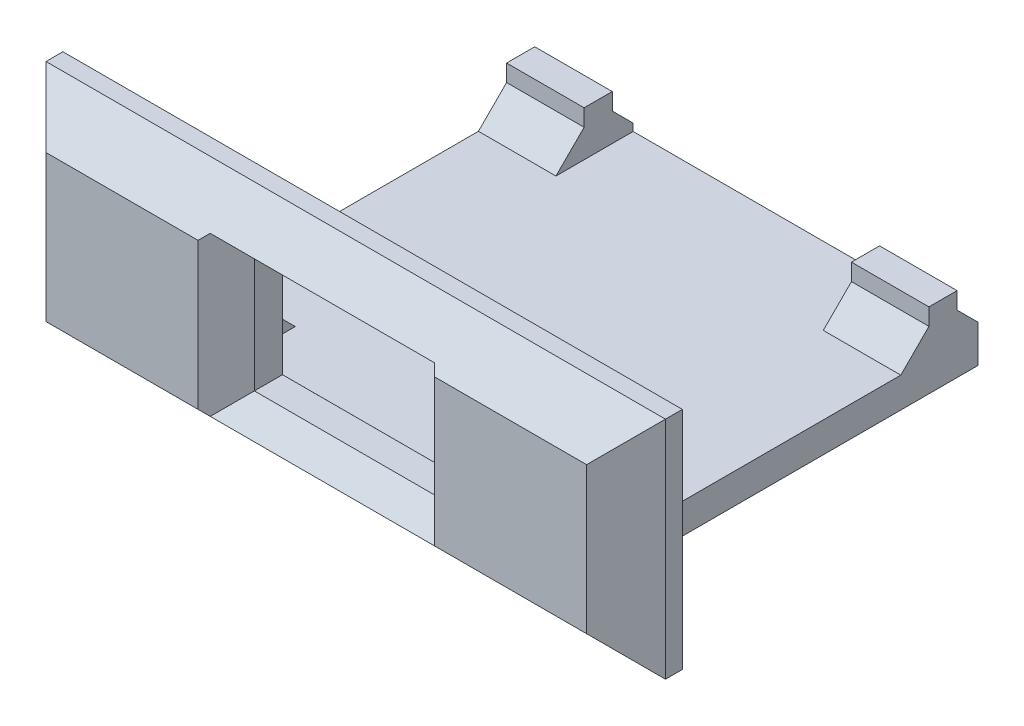
SolidWorks part; units mm, degrees
ref_plane "Спереди" through (0, 0, 0) normal (0, 0, 1) x (1, 0, 0)
ref_plane "Сверху" through (0, 0, 0) normal (0, 1, 0) x (1, 0, 0)
ref_plane "Справа" through (0, 0, 0) normal (1, 0, 0) x (0, 0, -1)
ref_plane "Плоскость4" through (0, 0, 727.8525) normal (0, 0, 1) x (1, 0, 0)
sketch "Эскиз1" plane through (0, 0, 727.8525) normal (0, 0, 1) x (1, 0, 0)
  line L0 (-220.0776, -84.8681) -> (-220.0776, -72.8681)
  line L1 (-208.0776, -72.8681) -> (-122.0776, -72.8681)
  line L2 (-220.0776, -84.8681) -> (-220.0776, -100.8681)
  line L3 (-208.0776, -112.8681) -> (-122.0776, -112.8681)
  line L4 (-110.0776, -84.8681) -> (-110.0776, -100.8681)
  line L5 (-208.0776, -72.8681) -> (-220.0776, -72.8681)
  line L6 (-122.0776, -72.8681) -> (-110.0776, -72.8681)
  line L7 (-110.0776, -84.8681) -> (-110.0776, -72.8681)
  line L8 (-208.0776, -112.8681) -> (-220.0776, -112.8681)
  line L9 (-220.0776, -100.8681) -> (-220.0776, -112.8681)
  line L10 (-110.0776, -100.8681) -> (-110.0776, -112.8681)
  line L11 (-122.0776, -112.8681) -> (-110.0776, -112.8681)
  point P6 (-110.0776, -112.8681)
  point P11 (-220.0776, -112.8681)
  point P14 (-220.0776, -72.8681)
  dimension "D1" = 110
  dimension "D2" = 40
extrude "Бобышка-Вытянуть1" add sketch "Эскиз1" along normal blind 10
sketch "Эскиз2" plane through (0, 0, 737.8525) normal (0, 0, 1) x (1, 0, 0)
  line L8 (-220.0776, -92.8681) -> (-110.0776, -92.8681) construction
  line L9 (-220.0776, -72.8681) -> (-220.0776, -112.8681) construction
  line L10 (-110.0776, -112.8681) -> (-110.0776, -72.8681) construction
  line L11 (-165.0776, -72.8681) -> (-165.0776, -112.8681) construction
  line L12 (-110.0776, -72.8681) -> (-220.0776, -72.8681) construction
  line L13 (-220.0776, -112.8681) -> (-110.0776, -112.8681) construction
  line L18 (-181.0776, -82.7081) -> (-181.0776, -103.0281)
  line L19 (-181.0776, -103.0281) -> (-149.0776, -103.0281)
  line L20 (-149.0776, -103.0281) -> (-149.0776, -82.7081)
  line L21 (-149.0776, -82.7081) -> (-181.0776, -82.7081)
  point P2 (-181.0776, -92.8681)
  point P16 (-165.0776, -82.7081)
  dimension "D1" = 20.32
  dimension "D2" = 20.32
  dimension "D3" = 32
extrude "Вырез-Вытянуть1" cut sketch "Эскиз2" against normal up to surface (10 mm away) up to face at (-165.0776, -92.8681, 727.8525)
ref_plane "Плоскость5" through (-165.0776, 0, 0) normal (1, 0, 0) x (0, 0, -1)
ref_plane "Плоскость6" through (0, -103.0281, 0) normal (0, 1, 0) x (1, 0, 0)
ref_plane "Плоскость7" through (0, 0, 727.8525) normal (0, 0, -1) x (-1, 0, 0)
fillet "Скругление1" radius 0.01 1 edges at (-165.0776, -103.0281, 727.8525)
fillet "Скругление2" radius 0.01 3 edges at (-149.0776, -92.8731, 727.8525) (-165.0776, -82.7081, 727.8525) (-181.0776, -92.8731, 727.8525)
sketch "Эскиз3" plane through (0, 0, 727.8525) normal (0, 0, -1) x (-1, 0, 0)
  line L0 (188.6126, -104.4966) -> (141.5426, -104.4966) construction
  line L1 (127.5776, -104.4966) -> (202.5776, -104.4966)
  line L2 (127.5776, -104.4966) -> (127.5776, -112.8681)
  line L3 (127.5776, -112.8681) -> (202.5776, -112.8681)
  line L4 (202.5776, -104.4966) -> (202.5776, -112.8681)
  line L5 (165.0776, -72.8681) -> (165.0776, -133.1733) construction
  point P6 (165.0776, -104.4966)
  dimension "D1" = 75
  dimension "D4" = 8.3715
extrude "Бобышка-Вытянуть2" add sketch "Эскиз3" along normal blind 70
sketch "Эскиз4" plane through (0, -104.4966, 0) normal (0, 1, 0) x (1, 0, 0)
  line L0 (-202.5776, -657.8525) -> (-202.5776, -727.8525) construction
  line L1 (-202.5776, -661.5629) -> (-188.8126, -661.5629)
  line L2 (-202.5776, -661.5629) -> (-202.5776, -666.5629)
  line L3 (-202.5776, -666.5629) -> (-188.8126, -666.5629)
  line L4 (-188.8126, -661.5629) -> (-188.8126, -666.5629)
  line L5 (-141.3426, -661.5629) -> (-127.5776, -661.5629)
  line L6 (-141.3426, -661.5629) -> (-141.3426, -666.5629)
  line L7 (-141.3426, -666.5629) -> (-127.5776, -666.5629)
  line L8 (-127.5776, -661.5629) -> (-127.5776, -666.5629)
  line L9 (-202.5776, -722.8525) -> (-188.8126, -722.8525)
  line L10 (-202.5776, -722.8525) -> (-202.5776, -727.8525)
  line L11 (-202.5776, -727.8525) -> (-188.8126, -727.8525)
  line L12 (-188.8126, -722.8525) -> (-188.8126, -727.8525)
  line L14 (-127.5776, -657.8525) -> (-127.5776, -727.8525) construction
  line L15 (-141.3426, -727.8525) -> (-127.5776, -727.8525)
  line L16 (-141.3426, -727.8525) -> (-141.3426, -722.8525)
  line L17 (-141.3426, -722.8525) -> (-127.5776, -722.8525)
  line L18 (-127.5776, -727.8525) -> (-127.5776, -722.8525)
  dimension "D1" = 5
  dimension "D2" = 5
  dimension "D3" = 5
  dimension "D4" = 5
  dimension "D5" = 13.765
  dimension "D6" = 13.765
  dimension "D7" = 13.765
  dimension "D8" = 13.765
extrude "Бобышка-Вытянуть3" add sketch "Эскиз4" along normal blind 8
chamfer "Фаска1" distance 5 angle 45 8 edges at (-195.6951, -96.4966, 727.8525) (-134.4601, -96.4966, 727.8525) (-134.4601, -104.4966, 666.5629) (-134.4601, -104.4966, 722.8525) (-134.4601, -104.4966, 661.5629) (-195.6951, -104.4966, 661.5629) (-195.6951, -104.4966, 722.8525) (-195.6951, -104.4966, 666.5629)
sketch "Эскиз5" plane through (0, -112.8681, 0) normal (0, -1, 0) x (1, 0, 0)
  line L0 (-22, 727.8525) -> (22, 727.8525) construction
  line L1 (-127.5776, 657.8525) -> (-202.5776, 657.8525)
  line L2 (-127.5776, 657.8525) -> (-127.5776, 727.8525)
  line L3 (-127.5776, 727.8525) -> (-202.5776, 727.8525)
  line L4 (-202.5776, 657.8525) -> (-202.5776, 727.8525)
  line L5 (14.8081, 727.8525) -> (-14.8081, 727.8525) construction
extrude "Вырез-Вытянуть2" cut sketch "Эскиз5" against normal blind 3
chamfer "Фаска2" distance 7 angle 45 4 edges at (-110.0776, -92.8681, 737.8525) (-165.0776, -72.8681, 737.8525) (-220.0776, -92.8681, 737.8525) (-165.0776, -112.8681, 737.8525)
chamfer "Фаска3" distance 5 angle 45 3 edges at (-181.0776, -92.8681, 737.8525) (-165.0776, -82.7081, 737.8525) (-149.0776, -92.8681, 737.8525)
chamfer "Фаска4" distance 5 angle 45 1 edges at (-165.0776, -103.0281, 737.8525)
